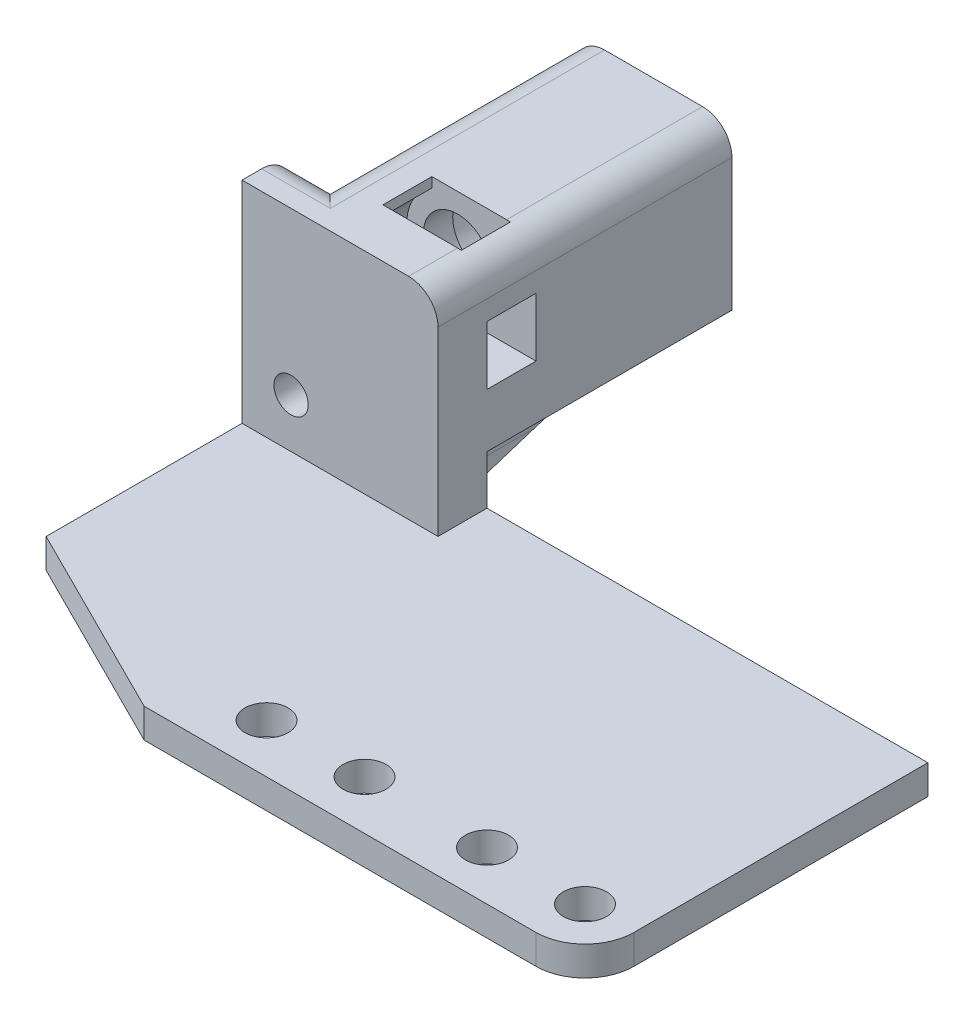
SolidWorks part; units mm, degrees
other "标注1"
sketch "草图59" plane through (-20, 24.5, -60) normal (-0.6869, 0.629, -0.3641) x (-0.701, -0.4413, 0.5602)
ref_plane "前视基准面" through (0, 0, 0) normal (0, 0, 1) x (1, 0, 0)
ref_plane "上视基准面" through (0, 0, 0) normal (0, 1, 0) x (1, 0, 0)
ref_plane "右视基准面" through (0, 0, 0) normal (1, 0, 0) x (0, 0, -1)
sketch "草图4" plane through (0, 0, 0) normal (0, 1, 0) x (1, 0, 0)
  line L1 (0, 0) -> (25, 0)
  line L2 (0, 0) -> (0, 10)
  line L3 (0, 10) -> (25, 10)
  line L4 (25, 0) -> (25, 10)
  dimension "D1" = 25
  dimension "D2" = 10
extrude "凸台-拉伸1" add sketch "草图4" along normal blind 3
sketch "草图5" plane through (0, 3, 0) normal (0, 1, 0) x (1, 0, 0)
  line L0 (12.5, 10) -> (12.5, 0)
  line L1 (25, 10) -> (0, 10) construction
  line L2 (0, 0) -> (25, 0) construction
  line L3 (12.5, 5) -> (7.5, 5)
  line L4 (12.5, 5) -> (17.5, 5)
  dimension "D1" = 5
  dimension "D2" = 5
sketch "草图6" plane through (0, 3, 0) normal (0, 1, 0) x (1, 0, 0)
  point P0 (7.5, 5)
  point P3 (17.5, 5)
hole_wizard "Ø4.4 (4.4) 直径孔1" positions "草图6" profile "草图7" hole size "Ø4.4" standard "GB" end condition through all
sketch "草图7" plane through (7.5, 3, -5) normal (1, 0, 0) x (0, 0, 1)
  line L0 (0, 0) -> (0, 3)
  line L1 (0, 3) -> (2.2, 3)
  line L2 (2.2, 3) -> (2.2, 0)
  line L5 (2.2, 0) -> (0, 0)
  line L11 (0, -6.35) -> (0, 107.95) construction
  dimension "通孔孔直径" = 4.4
  dimension "通孔孔深度" = 3
sketch "草图8" plane through (0, 0, 0) normal (0, -1, 0) x (1, 0, 0)
  line L1 (0, -10) -> (65, -10)
  line L2 (0, -10) -> (0, -35)
  line L3 (0, -35) -> (65, -35)
  line L4 (65, -10) -> (65, -35)
  dimension "D1" = 25
  dimension "D2" = 65
extrude "凸台-拉伸2" add sketch "草图8" against normal blind 3
sketch "草图9" plane through (0, 3, 0) normal (0, 1, 0) x (1, 0, 0)
  line L0 (65, 35) -> (65, 10) construction
  line L1 (0, 35) -> (65, 35)
  line L2 (0, 35) -> (0, 30)
  line L3 (0, 30) -> (65, 30)
  line L4 (65, 35) -> (65, 30)
  line L6 (0, 35) -> (30, 35)
  line L7 (0, 35) -> (0, 30)
  line L8 (0, 30) -> (30, 30)
  line L9 (30, 35) -> (30, 30)
  dimension "D1" = 5
  dimension "D2" = 30
sketch "草图11" plane through (0, 0, -35) normal (0, 0, -1) x (-1, 0, 0)
sketch "草图13" plane through (0, 0, -35) normal (0, 0, -1) x (-1, 0, 0)
sketch "草图16" plane through (0, 3, 0) normal (0, 1, 0) x (1, 0, 0)
  line L0 (25, 0) -> (65, 10)
  line L1 (65, 10) -> (25, 10)
  line L2 (65, 10) -> (25, 10) construction
  line L3 (25, 0) -> (25, 10) construction
  line L4 (25, 10) -> (25, 0)
sketch "草图18" plane through (0, 3, 0) normal (0, 1, 0) x (1, 0, 0)
  line L0 (12.5, 10) -> (45, 10)
  line L1 (65, 10) -> (25, 10) construction
  line L2 (45, 10) -> (45, 35)
  line L3 (0, 35) -> (65, 35) construction
  line L4 (45, 35) -> (65, 35)
  line L5 (65, 35) -> (65, 10)
  line L6 (65, 10) -> (45, 10)
  line M7 (25, 10) -> (65, 10)
  line M8 (65, 10) -> (65, 35)
  line M9 (65, 35) -> (0, 35)
  dimension "D1" = 32.5
extrude "切除-拉伸1" cut sketch "草图18" against normal blind 10 contours L2 M7 M8 M9
sketch "草图19" plane through (0, 3, 0) normal (0, 1, 0) x (1, 0, 0)
  line L0 (65, 10) -> (25, 10) construction
  line L1 (0, 35) -> (-20, 35)
  line L2 (0, 35) -> (0, 10)
  line L3 (0, 10) -> (-20, 10)
  line L4 (-20, 35) -> (-20, 10)
  line L5 (12.5, 10) -> (12.5, 0) construction
  dimension "D1" = 32.5
extrude "凸台-拉伸3" add sketch "草图19" against normal blind 3
sketch "草图20" plane through (0, 3, 0) normal (0, 1, 0) x (1, 0, 0)
  line L0 (-20, 10) -> (0, 10)
  line L1 (0, 10) -> (0, 0)
  line L2 (0, 0) -> (-20, 10)
  line L3 (25, 10) -> (45, 10)
  line L4 (45, 10) -> (25, 0)
  line L5 (25, 0) -> (25, 10)
extrude "凸台-拉伸4" add sketch "草图20" against normal blind 3
sketch "草图21" plane through (0, 3, 0) normal (0, 1, 0) x (1, 0, 0)
  line L0 (45, 10) -> (45, 35) construction
  line L1 (-20, 35) -> (45, 35)
  line L2 (-20, 35) -> (-20, 30)
  line L3 (-20, 30) -> (45, 30)
  line L4 (45, 35) -> (45, 30)
  dimension "D1" = 5
extrude "凸台-拉伸5" add sketch "草图21" along normal blind 15
sketch "草图23" plane through (0, 18, 0) normal (0, 1, 0) x (1, 0, 0)
  line L0 (0, 30) -> (65, 30) construction
  line L1 (-20, 35) -> (-20, 30) construction
  line L3 (12.5, 30) -> (45, 30)
  line L4 (12.5, 30) -> (12.5, 35)
  line L5 (12.5, 35) -> (45, 35)
  line L6 (45, 30) -> (45, 35)
  point P0 (12.5, 30)
  dimension "D1" = 32.5
extrude "切除-拉伸2" cut sketch "草图23" against normal blind 15
sketch "草图24" plane through (0, 0, -30) normal (0, 0, 1) x (1, 0, 0)
  line L0 (-20, 3) -> (12.5, 3) construction
  line L1 (-20, 18) -> (-20, 3) construction
  point P0 (-15, 8)
  dimension "D1" = 5
  dimension "D2" = 5
sketch "草图25" plane through (0, 0, -30) normal (0, 0, 1) x (1, 0, 0)
  point P0 (-15, 8)
hole_wizard "Ø3.5 (3.5) 直径孔1" positions "草图25" profile "草图26" hole size "Ø3.5" standard "GB" end condition through all
sketch "草图26" plane through (-15, 8, -30) normal (1, 0, 0) x (0, -1, 0)
  line L0 (0, 0) -> (0, 5)
  line L1 (0, 5) -> (1.75, 5)
  line L2 (1.75, 5) -> (1.75, 0)
  line L5 (1.75, 0) -> (0, 0)
  line L11 (0, -6.35) -> (0, 107.95) construction
  dimension "通孔孔直径" = 3.5
  dimension "通孔孔深度" = 5
sketch "草图28" plane through (0, 3, 0) normal (0, 1, 0) x (1, 0, 0)
  line L0 (65, 10) -> (25, 10) construction
  line L1 (45, 35) -> (63, 35)
  line L2 (45, 35) -> (45, 10)
  line L3 (45, 10) -> (63, 10)
  line L4 (63, 35) -> (63, 10)
  dimension "D1" = 18
extrude "凸台-拉伸6" add sketch "草图28" against normal blind 3
sketch "草图30" plane through (0, 3, 0) normal (0, 1, 0) x (1, 0, 0)
  line L0 (0, 35) -> (65, 35) construction
  line L1 (63, 10) -> (48, 10)
  line L2 (63, 10) -> (63, 35)
  line L3 (63, 35) -> (48, 35)
  line L4 (48, 10) -> (48, 35)
  dimension "D1" = 15
extrude "凸台-拉伸8" add sketch "草图30" along normal blind 15
sketch "草图31" plane through (0, 0, -35) normal (0, 0, -1) x (-1, 0, 0)
  line L0 (-48, 18) -> (-48, 3) construction
  line L1 (-63, 18) -> (-48, 18) construction
  point P0 (-55.5, 10.5)
  dimension "D1" = 7.5
  dimension "D2" = 7.5
hole_wizard "孔1" positions "草图32" profile "草图33" legacy
sketch "草图32" plane through (0, 0, -35) normal (0, 0, -1) x (-1, 0, 0)
  point P0 (-55.5, 10.5)
sketch "草图33" plane through (55.5, 10.5, -35) normal (1, 0, 0) x (0, 1, 0)
  line L0 (0, 0) -> (0, 25)
  line L1 (0, 25) -> (5.1, 25)
  line L2 (5.1, 25) -> (5.1, 0)
  line L3 (5.1, 0) -> (0, 0)
  line L4 (0, 110) -> (0, -10) construction
  dimension "直径" = 10.2
  dimension "深度" = 25
sketch "草图35" plane through (0, 0, -10) normal (0, 0, 1) x (1, 0, 0)
  line L0 (48, 18) -> (45, 3)
  line L1 (45, 0) -> (63, 0)
  line L2 (45, 0) -> (45, 3)
  line L3 (48, 18) -> (63, 18)
  line L4 (63, 0) -> (63, 18)
extrude "凸台-拉伸9" add sketch "草图35" along normal blind 3
sketch "草图36" plane through (0, 3, 0) normal (0, 1, 0) x (1, 0, 0)
  line L0 (25, 0) -> (45, 7)
  line L1 (45, 7) -> (45, 10)
  line L2 (65, 10) -> (25, 10) construction
  line L3 (45, 10) -> (25, 0)
extrude "凸台-拉伸10" add sketch "草图36" against normal blind 3
hole_wizard "孔2" positions "草图37" profile "草图38" legacy
sketch "草图37" plane through (0, 0, -10) normal (0, 0, -1) x (-1, 0, 0)
  point P0 (-55.5, 10.5)
sketch "草图38" plane through (55.5, 10.5, -10) normal (1, 0, 0) x (0, 1, 0)
  line L0 (0, 0) -> (0, 3)
  line L1 (0, 3) -> (3, 3)
  line L2 (3, 3) -> (3, 0)
  line L3 (3, 0) -> (0, 0)
  line L4 (0, 110) -> (0, -10) construction
  dimension "直径" = 6
  dimension "深度" = 3
fillet "圆角4" radius 3 1 edges at (63, 18, -21)
sketch "草图39" plane through (0, 0, 0) normal (0, -1, 0) x (1, 0, 0)
  line L1 (45, -7) -> (63, -7)
  line L2 (45, -7) -> (45, -35)
  line L3 (45, -35) -> (63, -35)
  line L4 (63, -7) -> (63, -35)
extrude "切除-拉伸3" cut sketch "草图39" against normal through all
sketch "草图40" plane through (0, 0, -35) normal (0, 0, -1) x (-1, 0, 0)
  line L0 (-45, 3) -> (-45, 0) construction
  line L1 (20, 18) -> (-45, 18)
  line L2 (20, 18) -> (20, 25)
  line L3 (20, 25) -> (-45, 25)
  line L4 (-45, 18) -> (-45, 25)
  line L6 (-45, 3) -> (-12.5, 3)
  line L7 (-45, 3) -> (-45, 18)
  line L8 (-45, 18) -> (-12.5, 18)
  line L9 (-12.5, 3) -> (-12.5, 18)
  line M8 (20, 18) -> (-12.5, 18)
  line M9 (-12.5, 18) -> (-12.5, 3)
  line M10 (-12.5, 3) -> (-45, 3)
  dimension "D1" = 7
extrude "凸台-拉伸11" add sketch "草图40" against normal blind 5 contours L7 L1 M10 M9 | L4 L1 L2 L3 M8
sketch "草图41" plane through (0, 0, -35) normal (0, 0, -1) x (-1, 0, 0)
  line L0 (15, 8) -> (8, 8)
  line L1 (8, 8) -> (8, 19)
  line L2 (20, 25) -> (-45, 25) construction
  line L3 (16, 8) -> (0, 8)
  line L4 (16, 8) -> (16, 25)
  line L5 (16, 25) -> (0, 25)
  line L6 (0, 8) -> (0, 25)
  line L8 (20, 0) -> (20, 25) construction
  circle A0 centre (8, 19) radius 5.2
  dimension "D2" = 10.4
  dimension "D1" = 12
  dimension "D3" = 11
  dimension "D4" = 8
  dimension "D5" = 8
extrude "凸台-拉伸12" add sketch "草图41" along normal blind 25
ref_plane "基准面1" through (0, 0, -40) normal (0, 0, -1) x (-1, 0, 0)
sketch "草图45" plane through (0, 0, -40) normal (0, 0, -1) x (-1, 0, 0)
  circle A0 centre (8, 19) radius 5.2
  circle A1 centre (8, 19) radius 3.5
  dimension "D1" = 7
extrude "凸台-拉伸15" add sketch "草图45" along normal blind 3
sketch "草图46" plane through (-16, 0, 0) normal (-1, 0, 0) x (0, 0, 1)
  line L0 (-35, 25) -> (-35, 8)
  line L1 (-35, 8) -> (-40, 8)
  line L2 (-40, 4.4) -> (-40, -4.4) construction
  line L3 (-60, 8) -> (-35, 8) construction
  line L4 (-40, 8) -> (-40, 25)
  line L5 (-60, 25) -> (-35, 25) construction
  line L6 (-40, 25) -> (-35, 25)
  line L7 (-40, 16.5) -> (-35, 16.5)
  line L8 (-35, 16.5) -> (-35, 13.5)
  line L10 (-35, 13.5) -> (-40, 13.5)
  line L11 (-35, 13.5) -> (-35, 19.5)
  line L12 (-35, 19.5) -> (-40, 19.5)
  line L13 (-40, 13.5) -> (-40, 19.5)
  dimension "D1" = 3
  dimension "D2" = 6
extrude "切除-拉伸4" cut sketch "草图46" against normal through all contours L0 L12 L4 L7 | L10 L0 L7 L4
sketch "草图47" plane through (0, 8, 0) normal (0, -1, 0) x (1, 0, 0)
  line L0 (-6.625, -60) -> (-6.625, -35)
  line L1 (-13.25, -60) -> (0, -60) construction
  line L2 (0, -35) -> (65, -35) construction
sketch "草图48" plane through (0, 0, -35) normal (0, 0, -1) x (-1, 0, 0)
  line L0 (6.625, 8) -> (6.625, 0)
  line L1 (13.25, 8) -> (0, 8) construction
  line L2 (20, 0) -> (-45, 0) construction
ref_plane "基准面2" through (-6.625, 0, 0) normal (1, 0, 0) x (0, 0, -1)
sketch "草图50" plane through (0, 25, 0) normal (0, 1, 0) x (1, 0, 0)
  line L0 (-20, 35) -> (45, 35)
  line L1 (-6.625, 60) -> (-6.625, 35) construction
  line L2 (-10.625, 35) -> (-2.625, 35)
  line L3 (-10.625, 35) -> (-10.625, 40)
  line L4 (-10.625, 40) -> (-2.625, 40)
  line L5 (-2.625, 35) -> (-2.625, 40)
  dimension "D1" = 5
  dimension "D2" = 4
  dimension "D3" = 4
extrude "切除-拉伸5" cut sketch "草图50" against normal blind 4 contours L0 L5 L4 L3
sketch "草图51" plane through (0, 0, -60) normal (0, 0, -1) x (-1, 0, 0)
  line L0 (16, 13.5) -> (10.5, 8)
  line L1 (13.25, 8) -> (0, 8) construction
  line L2 (16, 9.4361) -> (16, 13.5) construction
  line L3 (16, 13.5) -> (16, 8)
  line L4 (16, 8) -> (10.5, 8)
  dimension "D1" = 45
extrude "切除-拉伸6" cut sketch "草图51" against normal blind 25
sketch "草图52" plane through (0, 0, -60) normal (0, 0, -1) x (-1, 0, 0)
  line L0 (6.625, 8) -> (16, 13.5)
  line L1 (16, 13.5) -> (10.5, 8)
  line L2 (10.5, 8) -> (6.625, 8)
extrude "切除-拉伸7" cut sketch "草图52" against normal blind 25
sketch "草图53" plane through (0, 0, -35) normal (0, 0, -1) x (-1, 0, 0)
  circle A0 centre (15, 8) radius 2.8
  dimension "D1" = 5.6
sketch "草图54" plane through (-6.625, 0, 0) normal (1, 0, 0) x (0, 0, -1)
  line L0 (35, 0) -> (60, 8)
  line L1 (60, 8) -> (35, 8)
  line L2 (35, 8) -> (35, 0)
extrude "凸台-拉伸16" add sketch "草图54" along normal blind 2
fillet "圆角6" radius 5 2 edges at (-6.625, 8, -47.5) (-4.625, 8, -47.5)
sketch "草图56" plane through (0, 25, 0) normal (0, 1, 0) x (1, 0, 0)
  line L1 (-20, 30) -> (45.7023, 30)
  line L2 (-20, 30) -> (-20, 61.9461)
  line L3 (-20, 61.9461) -> (45.7023, 61.9461)
  line L4 (45.7023, 30) -> (45.7023, 61.9461)
extrude "切除-拉伸10" cut sketch "草图56" against normal blind 0.5
sketch "草图57" plane through (0, 0, -35) normal (0, 0, -1) x (-1, 0, 0)
  line L0 (15, 8) -> (20, 8)
  line L1 (20, 0) -> (20, 24.5) construction
  line L2 (15, 8) -> (15, 0)
  line L3 (20, 0) -> (6.625, 0) construction
sketch "草图58" plane through (0, 0, -35) normal (0, 0, -1) x (-1, 0, 0)
  line L1 (-45, 3) -> (0, 3)
  line L2 (-45, 3) -> (-45, 24.5)
  line L3 (-45, 24.5) -> (0, 24.5)
  line L4 (0, 3) -> (0, 24.5)
extrude "切除-拉伸11" cut sketch "草图58" against normal blind 10
fillet "圆角7" radius 3 3 edges at (-2.625, 24.5, -37.5) (-16, 24.5, -47.5) (0, 24.5, -45)
sketch "草图60" plane through (0, 3, 0) normal (0, 1, 0) x (1, 0, 0)
  line L0 (45, 7) -> (45, 0)
  line L1 (25, 0) -> (45, 0)
  line L2 (25, 0) -> (45, 7)
extrude "凸台-拉伸17" add sketch "草图60" against normal blind 3
sketch "草图61" plane through (0, 3, 0) normal (0, 1, 0) x (1, 0, 0)
  line L0 (65, 10) -> (25, 10) construction
  line L1 (25, 0) -> (45, 0)
  line L2 (25, 0) -> (25, 10)
  line L3 (25, 10) -> (45, 10)
  line L4 (45, 0) -> (45, 10)
  line L5 (25, 5) -> (45, 5)
  point P9 (35, 5)
  point P10 (30, 5)
  point P11 (40, 5)
  dimension "D1" = 5
  dimension "D2" = 5
sketch "草图62" plane through (0, 3, 0) normal (0, 1, 0) x (1, 0, 0)
  point P0 (30, 5)
  point P3 (40, 5)
hole_wizard "Ø4.4 (4.4) 直径孔2" positions "草图62" profile "草图63" hole size "Ø4.4" standard "GB" end condition through all
sketch "草图63" plane through (30, 3, -5) normal (1, 0, 0) x (0, 0, 1)
  line L0 (0, 0) -> (0, 3)
  line L1 (0, 3) -> (2.2, 3)
  line L2 (2.2, 3) -> (2.2, 0)
  line L5 (2.2, 0) -> (0, 0)
  line L11 (0, -6.35) -> (0, 107.95) construction
  dimension "通孔孔直径" = 4.4
  dimension "通孔孔深度" = 3
fillet "圆角8" radius 5 1 edges at (45, 1.5, 0)
